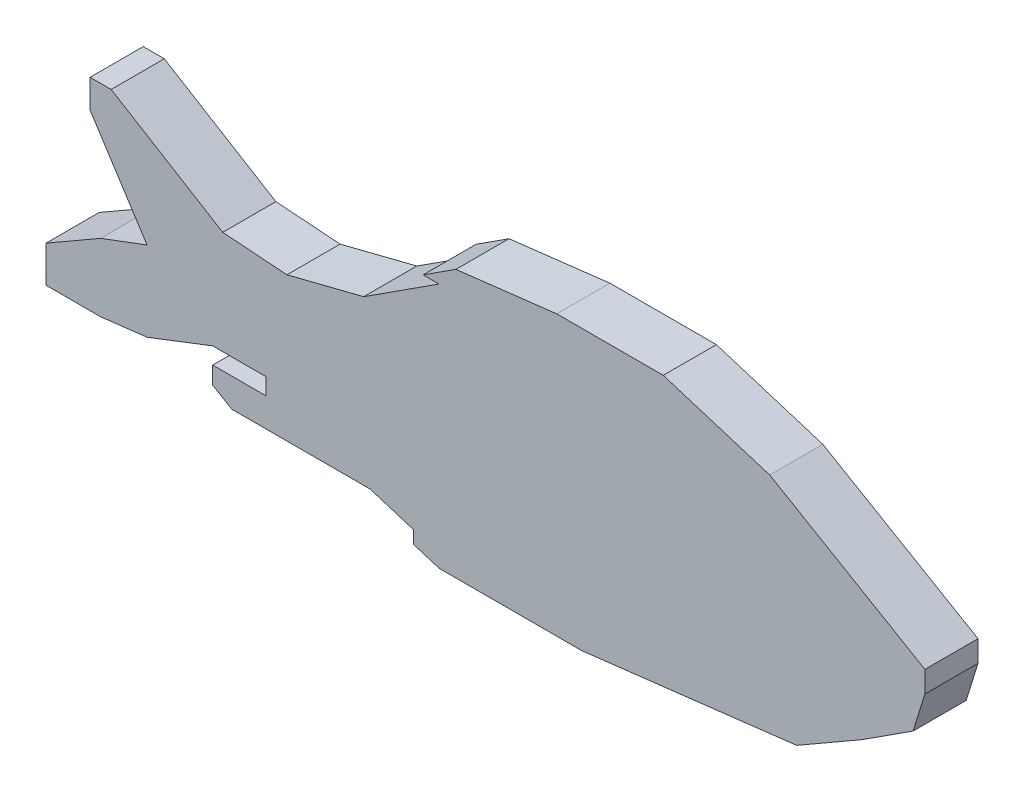
SolidWorks part; units mm, degrees
ref_plane "Спереди" through (0, 0, 0) normal (0, 0, 1) x (1, 0, 0)
ref_plane "Сверху" through (0, 0, 0) normal (0, 1, 0) x (1, 0, 0)
ref_plane "Справа" through (0, 0, 0) normal (1, 0, 0) x (0, 0, -1)
sketch "Эскиз1" plane through (0, 0, 0) normal (0, 0, 1) x (1, 0, 0)
  line L0 (229.0009, 493.6485) -> (1509.0009, 493.6485) construction
  line L7 (-69.9519, 0) -> (-80.6697, 16.6181)
  line L8 (-80.6697, 16.6181) -> (-80.6697, 21.977)
  line L9 (-80.6697, 21.977) -> (-76.7088, 21.977)
  line L10 (-76.7088, 21.977) -> (-55.7042, 9.1891)
  line L11 (-55.7042, 9.1891) -> (-43.6234, 8.309)
  line L12 (-43.6234, 8.309) -> (-29.1777, 11.9582)
  line L13 (-29.1777, 11.9582) -> (-14.9905, 21.1082)
  line L14 (-14.9905, 21.1082) -> (-17.9939, 21.1082)
  line L15 (-17.9939, 21.1082) -> (-11.8234, 25.0878)
  line L16 (-11.8234, 25.0878) -> (7.1696, 27.3359)
  line L17 (7.1696, 27.3359) -> (27.2073, 27.3359)
  line L18 (27.2073, 27.3359) -> (47.2449, 21.1082)
  line L19 (47.2449, 21.1082) -> (69.1304, 8.309)
  line L20 (69.1304, 8.309) -> (76.4513, 4.0276)
  line L21 (76.4513, 4.0276) -> (76.4513, 0)
  line L22 (76.4513, 0) -> (74.2293, -7.1495)
  line L23 (74.2293, -7.1495) -> (64.5497, -13.3923)
  line L24 (64.5497, -13.3923) -> (52.3222, -20.4316)
  line L25 (52.3222, -20.4316) -> (37.2261, -22.2184)
  line L26 (37.2261, -22.2184) -> (11.8841, -25.218)
  line L27 (11.8841, -25.218) -> (-14.9905, -25.218)
  line L28 (-14.9905, -25.218) -> (-19.816, -23.7182)
  line L29 (-19.816, -23.7182) -> (-19.816, -21.325)
  line L30 (-19.816, -21.325) -> (-27.9542, -18.7957)
  line L31 (-27.9542, -18.7957) -> (-34.5596, -18.7957)
  line L32 (-34.5596, -18.7957) -> (-53.9814, -18.7957)
  line L33 (-53.9814, -18.7957) -> (-57.5891, -16.6858)
  line L34 (-57.5891, -16.6858) -> (-57.5891, -13.3923)
  line L35 (-57.5891, -13.3923) -> (-47.5609, -13.3923)
  line L36 (-47.5609, -13.3923) -> (-47.5609, -10.2709)
  line L37 (-47.5609, -10.2709) -> (-57.5891, -10.2709)
  line L38 (-57.5891, -10.2709) -> (-69.9519, -15.0391)
  line L39 (-69.9519, -15.0391) -> (-78.6893, -16.0732)
  line L40 (-78.6893, -16.0732) -> (-88.9727, -16.0732)
  line L41 (-88.9727, -16.0732) -> (-88.9727, -9.2087)
  line L42 (-88.9727, -9.2087) -> (-85.3957, -7.1495)
  line L43 (-85.3957, -7.1495) -> (-78.6893, -3.2886)
  line L44 (-78.6893, -3.2886) -> (-69.9519, 0)
extrude "Бобышка-Вытянуть1" add sketch "Эскиз1" along normal blind 10 contours L44 L7 L8 L9 L10 L11 L12 L13 L14 L15 L16 L17 L18 L19 L20 L21 L22 L23 L24 L25 L26 L27 L28 L29 L30 L31 L32 L33 L34 L35 L36 L37 L38 L39 L40 L41 L42 L43
